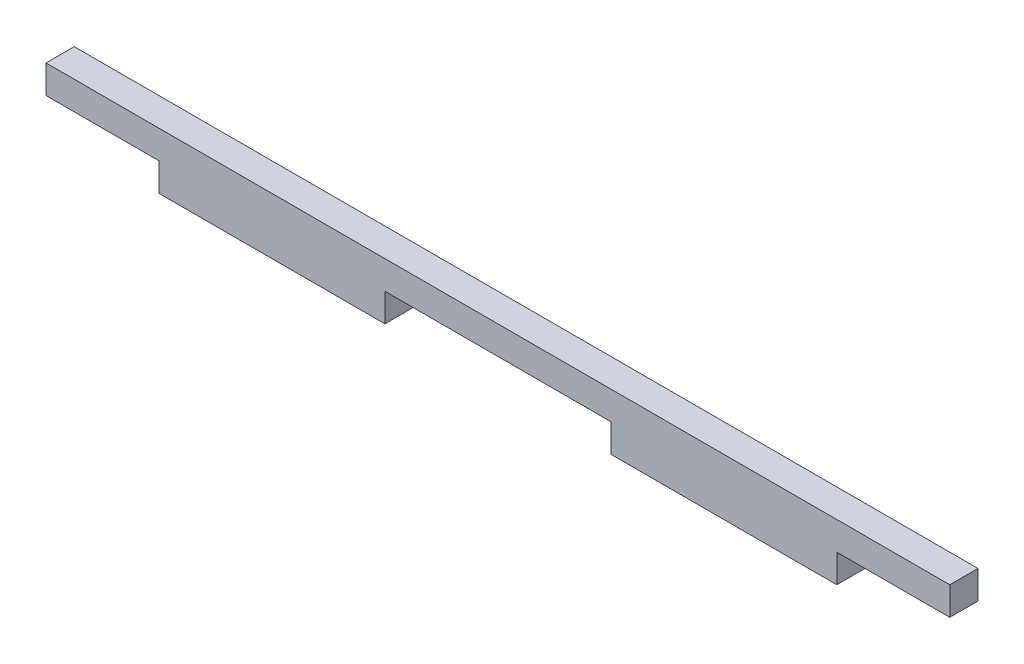
SolidWorks part; units mm, degrees
ref_plane "Front Plane" through (0, 0, 0) normal (0, 0, 1) x (1, 0, 0)
ref_plane "Top Plane" through (0, 0, 0) normal (0, 1, 0) x (1, 0, 0)
ref_plane "Right Plane" through (0, 0, 0) normal (1, 0, 0) x (0, 0, -1)
sketch "Sketch1" plane through (0, 0, 0) normal (0, 0, 1) x (1, 0, 0)
  line L0 (-12.7, -1.5875) -> (12.7, -1.5875)
  line L1 (-50.8, 1.5875) -> (50.8, 1.5875)
  line L2 (-50.8, 1.5875) -> (-50.8, -1.5875)
  line L3 (-50.8, -1.5875) -> (-38.1, -1.5875)
  line L4 (50.8, 1.5875) -> (50.8, -1.5875)
  line L5 (-50.8, 1.5875) -> (50.8, -1.5875) construction
  line L6 (-50.8, -1.5875) -> (50.8, 1.5875) construction
  line L8 (-12.7, -1.5875) -> (-12.7, -4.7625)
  line L9 (-12.7, -4.7625) -> (-38.1, -4.7625)
  line L10 (-38.1, -1.5875) -> (-38.1, -4.7625)
  line L12 (12.7, -1.5875) -> (12.7, -4.7625)
  line L13 (12.7, -4.7625) -> (38.1, -4.7625)
  line L14 (38.1, -1.5875) -> (38.1, -4.7625)
  line L15 (38.1, -1.5875) -> (50.8, -1.5875)
  point P0 (0, 0)
  dimension "D1" = 3.175
  dimension "D2" = 101.6
  dimension "D3" = 3.175
  dimension "D4" = 25.4
  dimension "D5" = 12.7
  dimension "D6" = 25.4
  dimension "D7" = 12.7
extrude "Boss-Extrude1" add sketch "Sketch1" along normal mid plane 3.175
